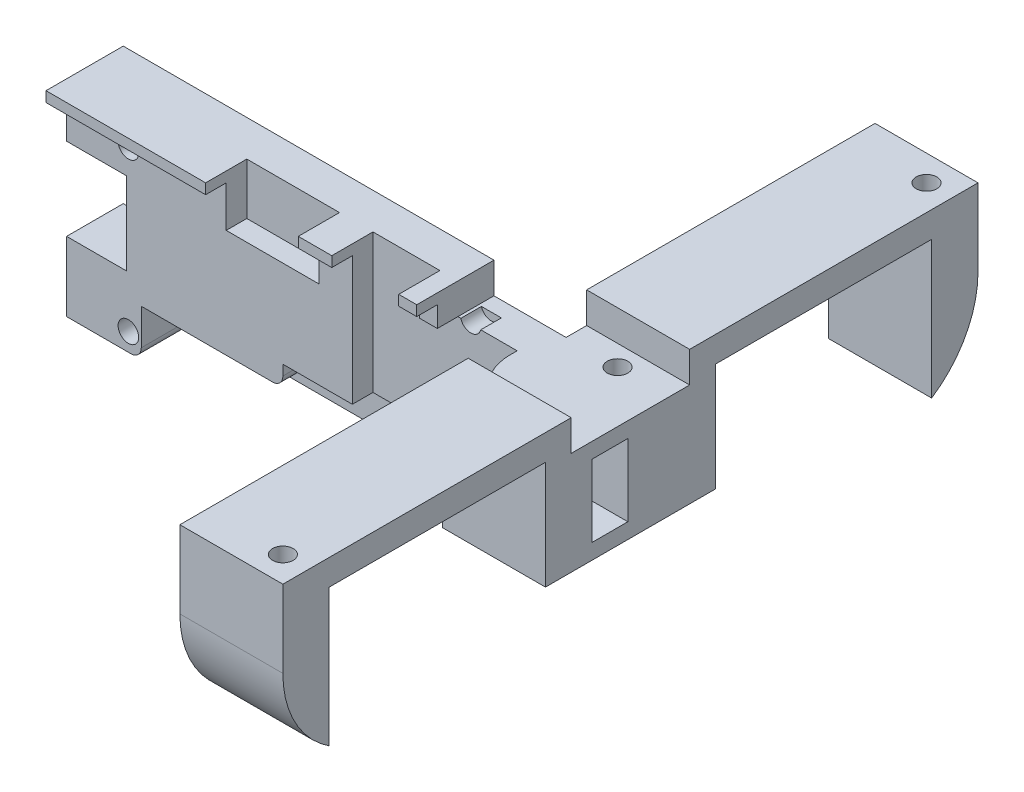
SolidWorks part; units mm, degrees
material "ABS"
ref_plane "Front Plane" through (0, 0, 0) normal (0, 0, 1) x (1, 0, 0)
ref_plane "Top Plane" through (0, 0, 0) normal (0, 1, 0) x (1, 0, 0)
ref_plane "Right Plane" through (0, 0, 0) normal (1, 0, 0) x (0, 0, -1)
sketch "Sketch1" plane through (0, 0, 0) normal (0, 1, 0) x (1, 0, 0)
  line L1 (-40.3176, 43.2333) -> (45.6824, 43.2333)
  line L2 (45.6824, 43.2333) -> (45.6824, -16.7667)
  line L3 (45.6824, -16.7667) -> (65.6824, -16.7667)
  line L4 (65.6824, -16.7667) -> (65.6824, 118.2333)
  line L7 (-40.3176, 43.2333) -> (-40.3176, 58.2333)
  line L8 (-40.3176, 58.2333) -> (45.6824, 58.2333)
  line L9 (45.6824, 58.2333) -> (45.6824, 118.2333)
  line L10 (45.6824, 118.2333) -> (65.6824, 118.2333)
  dimension "D1" = 20
  dimension "D2" = 60
  dimension "D3" = 86
  dimension "D4" = 15
  dimension "D5" = 60
  dimension "D6" = 20
extrude "Boss-Extrude1" add sketch "Sketch1" along normal blind 35
sketch "Sketch2" plane through (65.6824, 0, 0) normal (1, 0, 0) x (0, 0, -1)
  line L1 (-7.7667, 30) -> (34.2333, 30)
  line L2 (-7.7667, 30) -> (-7.7667, 9)
  line L3 (-7.7667, 9) -> (34.2333, 9)
  line L4 (34.2333, 30) -> (34.2333, 9)
  line L5 (-16.7667, 35) -> (-16.7667, 0) construction
  line L6 (50.7333, 24.6294) -> (50.7333, 59.3446) construction
  line L7 (-16.7667, 0) -> (118.2333, 0) construction
  line L9 (109.2333, 9) -> (67.2333, 9)
  line L10 (109.2333, 30) -> (109.2333, 9)
  line L11 (109.2333, 30) -> (67.2333, 30)
  line L12 (67.2333, 30) -> (67.2333, 9)
  dimension "D1" = 21
  dimension "D2" = 42
  dimension "D3" = 9
  dimension "D4" = 9
  dimension "D5" = 7.5
extrude "Cut-Extrude1" cut sketch "Sketch2" against normal up to next
sketch "Sketch3" plane through (45.6824, 0, 0) normal (-1, 0, 0) x (0, 0, 1)
  line L0 (7.7667, 9) -> (7.7667, 30) construction
  line L1 (-34.2333, 9) -> (7.7667, 9) construction
  line L2 (-50.7333, 32.1987) -> (-50.7333, 60.1119) construction
  line L3 (-43.2333, 35) -> (-43.2333, 0) construction
  circle A0 centre (11.2667, 24.75) radius 2
  circle A1 centre (11.2667, 15.25) radius 2
  circle A2 centre (-37.7333, 24.75) radius 2
  circle A3 centre (-37.7333, 15.25) radius 2
  circle A4 centre (-112.7333, 24.75) radius 2
  circle A5 centre (-112.7333, 15.25) radius 2
  circle A6 centre (-63.7333, 15.25) radius 2
  circle A7 centre (-63.7333, 24.75) radius 2
  dimension "D1" = 4
  dimension "D2" = 49
  dimension "D3" = 9.5
  dimension "D4" = 3.5
  dimension "D5" = 6.25
  dimension "D6" = 7.5
extrude "Cut-Extrude2" cut sketch "Sketch3" against normal blind 10
fillet "Fillet1" radius 20 2 edges at (55.6824, 0, 16.7667) (55.6824, 0, -118.2333)
sketch "Sketch6" plane through (65.6824, 0, 0) normal (1, 0, 0) x (0, 0, -1)
  line L0 (34.2333, 9) -> (34.2333, 30) construction
  line L1 (-7.7667, 9) -> (34.2333, 9)
  line L2 (-7.7667, 9) -> (-7.7667, 0)
  line L3 (-7.7667, 0) -> (34.2333, 0)
  line L4 (34.2333, 9) -> (34.2333, 0)
  line L5 (3.2333, 0) -> (98.2333, 0) construction
  line L6 (50.7333, 24.0053) -> (50.7333, 51.0852) construction
  line L7 (67.2333, 9) -> (67.2333, 0)
  line L8 (109.2333, 9) -> (67.2333, 9)
  line L9 (109.2333, 0) -> (67.2333, 0)
  line L10 (109.2333, 9) -> (109.2333, 0)
  dimension "D1" = 7.5
extrude "Cut-Extrude5" cut sketch "Sketch6" against normal up to next
sketch "Sketch7" plane through (-40.3176, 0, 0) normal (-1, 0, 0) x (0, 0, 1)
  line L0 (-58.2333, 0) -> (-43.2333, 0) construction
  line L2 (-58.2333, 35) -> (-43.2333, 35) construction
  line L3 (-43.2333, 35) -> (-43.2333, 0) construction
  circle A0 centre (-50.7333, 28.5) radius 2
  circle A1 centre (-50.7333, 5) radius 2
  dimension "D1" = 4
  dimension "D2" = 5
  dimension "D4" = 6.5
  dimension "D5" = 7.5
extrude "Cut-Extrude6" cut sketch "Sketch7" against normal blind 12
sketch "Sketch8" plane through (0, 0, 0) normal (0, -1, 0) x (1, 0, 0)
  line L1 (45.6824, -67.2333) -> (45.6824, -58.2333) construction
  line L2 (45.6824, -67.2333) -> (65.6824, -67.2333) construction
  line L3 (65.6824, -34.2333) -> (65.6824, -67.2333) construction
  line L4 (45.6824, -34.2333) -> (65.6824, -34.2333) construction
  line L5 (45.6824, -43.2333) -> (45.6824, -34.2333) construction
  line L9 (45.6824, -67.2333) -> (45.6824, -58.2333)
  line L10 (45.6824, -67.2333) -> (65.6824, -67.2333)
  line L11 (65.6824, -34.2333) -> (65.6824, -67.2333)
  line L12 (45.6824, -34.2333) -> (65.6824, -34.2333)
  line L13 (45.6824, -43.2333) -> (45.6824, -34.2333)
  line L16 (45.6824, -43.2333) -> (25.6824, -43.2333)
  line L17 (-40.3176, -43.2333) -> (45.6824, -43.2333) construction
  line L18 (25.6824, -43.2333) -> (25.6824, -58.2333)
  line L19 (45.6824, -58.2333) -> (-40.3176, -58.2333) construction
  line L20 (25.6824, -58.2333) -> (45.6824, -58.2333)
  dimension "D1" = 20
extrude "Cut-Extrude7" cut sketch "Sketch8" against normal blind 9
sketch "Sketch9" plane through (0, 9, 0) normal (0, -1, 0) x (1, 0, 0)
  line L1 (65.6824, -34.2333) -> (45.6824, -34.2333) construction
  line L2 (65.6824, -67.2333) -> (65.6824, -34.2333) construction
  line L3 (45.6824, -67.2333) -> (65.6824, -67.2333) construction
  circle A0 centre (55.6824, -42.2333) radius 2
  circle A1 centre (55.6824, -59.2333) radius 2
  dimension "D4" = 10
  dimension "D5" = 8
  dimension "D6" = 8
extrude "Cut-Extrude8" cut sketch "Sketch9" against normal blind 10
sketch "Sketch10" plane through (0, 35, 0) normal (0, 1, 0) x (1, 0, 0)
  line L0 (45.6824, 62.2333) -> (65.6824, 62.2333)
  line L1 (45.6824, 118.2333) -> (45.6824, 58.2333) construction
  line L2 (65.6824, -16.7667) -> (65.6824, 118.2333) construction
  line L3 (65.6824, 62.2333) -> (65.6824, 39.2333)
  line L4 (65.6824, 39.2333) -> (45.6824, 39.2333)
  line L5 (45.6824, 43.2333) -> (45.6824, -16.7667) construction
  line L7 (45.6824, 39.2333) -> (45.6824, 43.2333)
  line L8 (45.6824, 43.2333) -> (31.6824, 43.2333)
  line L9 (-40.3176, 43.2333) -> (45.6824, 43.2333) construction
  line L10 (31.6824, 43.2333) -> (31.6824, 58.2333)
  line L11 (45.6824, 58.2333) -> (-40.3176, 58.2333) construction
  line L12 (31.6824, 58.2333) -> (45.6824, 58.2333)
  line L13 (45.6824, 58.2333) -> (45.6824, 62.2333)
  dimension "D1" = 5
  dimension "D2" = 5
  dimension "D3" = 14
extrude "Cut-Extrude9" cut sketch "Sketch10" against normal blind 6
sketch "Sketch11" plane through (0, 29, 0) normal (0, 1, 0) x (1, 0, 0)
  line L0 (45.6824, 62.2333) -> (45.6824, 58.2333) construction
  circle A0 centre (55.6824, 58.2333) radius 2
  circle A1 centre (55.6824, 43.2333) radius 2
  dimension "D1" = 4
  dimension "D2" = 10
  dimension "D5" = 0
extrude "Cut-Extrude10" cut sketch "Sketch11" against normal blind 9
sketch "Sketch12" plane through (0, 35, 0) normal (0, 1, 0) x (1, 0, 0)
  line L0 (65.6824, 118.2333) -> (45.6824, 118.2333) construction
  line L1 (45.6824, -16.7667) -> (65.6824, -16.7667) construction
  line L2 (65.6824, -16.7667) -> (65.6824, 39.2333) construction
  line L3 (65.6824, 62.2333) -> (65.6824, 118.2333) construction
  circle A0 centre (60.6824, -11.7667) radius 2
  circle A1 centre (60.6824, 113.2333) radius 2
  dimension "D2" = 4
  dimension "D1" = 5
  dimension "D3" = 5
  dimension "D4" = 5
  dimension "D5" = 5
extrude "Cut-Extrude11" cut sketch "Sketch12" against normal blind 10
sketch "Sketch14" plane through (0, 0, -43.2333) normal (0, 0, 1) x (1, 0, 0)
  line L0 (-40.3176, 35) -> (-40.3176, 0) construction
  line L1 (-40.3176, 33) -> (42.6824, 33)
  line L2 (-40.3176, 33) -> (-40.3176, 0)
  line L3 (-40.3176, 0) -> (42.6824, 0)
  line L4 (42.6824, 33) -> (42.6824, 0)
  line L5 (-40.3176, 0) -> (25.6824, 0) construction
  line L7 (-40.3176, 35) -> (31.6824, 35) construction
  dimension "D1" = 83
  dimension "D2" = 2
extrude "Cut-Extrude13" cut sketch "Sketch14" against normal blind 4
sketch "Sketch15" plane through (0, 0, -47.2333) normal (0, 0, 1) x (1, 0, 0)
  line L1 (1.6824, 8) -> (33.6824, 8)
  line L3 (-25.8176, 0) -> (33.6824, 0)
  line L4 (33.6824, 8) -> (33.6824, 0)
  line L5 (31.6824, 29) -> (31.6824, 33) construction
  line L6 (-40.3176, 0) -> (25.6824, 0) construction
  line L7 (31.6824, 33) -> (-40.3176, 33) construction
  line L11 (1.6824, 8) -> (1.6824, 4)
  line L12 (1.6824, 4) -> (-25.8176, 4)
  line L13 (-25.8176, 4) -> (-25.8176, 0)
  line L14 (-40.3176, 33) -> (-40.3176, 0) construction
  dimension "D1" = 25
  dimension "D2" = 32
  dimension "D3" = 2
  dimension "D4" = 29
  dimension "D5" = 14.5
extrude "Cut-Extrude14" cut sketch "Sketch15" against normal blind 6.5
sketch "Sketch16" plane through (0, 0, 0) normal (0, -1, 0) x (1, 0, 0)
  line L0 (25.6824, -58.2333) -> (-40.3176, -58.2333) construction
  line L1 (-40.3176, -47.2333) -> (-25.8176, -47.2333)
  line L2 (-40.3176, -47.2333) -> (-40.3176, -58.2333)
  line L3 (-40.3176, -58.2333) -> (-25.8176, -58.2333)
  line L4 (-25.8176, -47.2333) -> (-25.8176, -58.2333)
  line L5 (-25.8176, -53.7333) -> (-25.8176, -47.2333) construction
extrude "Boss-Extrude2" add sketch "Sketch16" along normal blind 5
sketch "Sketch13" plane through (0, 0, -43.2333) normal (0, 0, 1) x (1, 0, 0)
  line L1 (-38.3176, 32) -> (36.6824, 32) construction
  line L2 (-38.3176, 32) -> (-38.3176, -4) construction
  line L3 (-38.3176, -4) -> (36.6824, -4) construction
  line L4 (36.6824, 32) -> (36.6824, -4) construction
  line L5 (-40.3176, 33) -> (-40.3176, -5) construction
  line L6 (-40.3176, 35) -> (31.6824, 35) construction
  circle A0 centre (-28.3176, 29.5) radius 2
  circle A1 centre (34.1824, 29.5) radius 2
  circle A2 centre (34.1824, -1.5) radius 2
  circle A3 centre (-28.3176, -1.5) radius 2
  dimension "D3" = 4
  dimension "D1" = 31
  dimension "D2" = 62.5
  dimension "D4" = 75
  dimension "D5" = 36
  dimension "D6" = 2.5
  dimension "D7" = 10
  dimension "D8" = 2
  dimension "D9" = 5.5
extrude "Cut-Extrude12" cut sketch "Sketch13" against normal blind 12
fillet "Fillet2" radius 2 1 edges at (-25.8176, -5, -52.7333)
fillet "Fillet3" radius 2 1 edges at (1.6824, 4, -50.4833)
sketch "Sketch17" plane through (0, 0, -43.2333) normal (0, 0, 1) x (1, 0, 0)
  line L1 (43.1824, -5) -> (15.1824, -5)
  line L2 (43.1824, -5) -> (43.1824, 29)
  line L4 (15.1824, -5) -> (15.1824, 35)
  line L5 (-40.3176, 35) -> (31.6824, 35) construction
  line L7 (-9.3176, 35) -> (8.6824, 35)
  line L8 (-9.3176, 35) -> (-9.3176, 25)
  line L9 (-9.3176, 25) -> (8.6824, 25)
  line L10 (8.6824, 35) -> (8.6824, 25)
  line L11 (15.1824, 35) -> (28.1824, 35)
  line L12 (28.1824, 35) -> (28.1824, 29)
  line L13 (28.1824, 29) -> (43.1824, 29)
  circle A1 centre (-28.3176, 29.5) radius 2 construction
  dimension "D3" = 19
  dimension "D1" = 13
  dimension "D2" = 6.5
  dimension "D4" = 18
  dimension "D5" = 10
  dimension "D6" = 40
  dimension "D7" = 15
  dimension "D8" = 6
extrude "Cut-Extrude15" cut sketch "Sketch17" against normal blind 8
sketch "Sketch20" plane through (0, 0, -47.2333) normal (0, 0, 1) x (1, 0, 0)
  line L0 (-40.3176, 33) -> (-40.3176, -5) construction
  line L1 (-40.3176, 24.5) -> (-32.3176, 24.5)
  line L2 (-40.3176, 24.5) -> (-40.3176, 8.5)
  line L3 (-40.3176, 8.5) -> (-32.3176, 8.5)
  line L4 (-32.3176, 24.5) -> (-32.3176, 8.5)
  circle A0 centre (-28.3176, 29.5) radius 2 construction
  dimension "D1" = 8
  dimension "D2" = 16
  dimension "D3" = 5
extrude "Cut-Extrude18" cut sketch "Sketch20" against normal up to next
chamfer "Chamfer1" distance 10 angle 20 1 edges at (-32.3176, 16.5, -47.2333) first distance on face at (-32.3176, 16.5, -52.7333)
sketch "Sketch21" plane through (0, 0, -47.2333) normal (0, 0, 1) x (1, 0, 0)
  line L0 (-38.3176, 32) -> (36.6824, 32) construction
  line L1 (-38.3176, 32) -> (-38.3176, -4) construction
  line L2 (-38.3176, -4) -> (36.6824, -4) construction
  line L3 (36.6824, 32) -> (36.6824, -4) construction
  line L5 (33.1824, 26.5) -> (39.1824, 26.5) construction
  line L6 (33.1824, 26.5) -> (33.1824, 14) construction
  line L7 (33.1824, 14) -> (39.1824, 14)
  line L8 (39.1824, 26.5) -> (39.1824, 14) construction
  line L9 (32.6824, 13) -> (37.6824, 13) construction
  line L10 (32.6824, 13) -> (32.6824, 3) construction
  line L11 (32.6824, 3) -> (37.6824, 3) construction
  line L12 (37.6824, 13) -> (37.6824, 3) construction
  circle A0 centre (-28.3176, 29.5) radius 2
  circle A1 centre (34.1824, 29.5) radius 2
  circle A2 centre (34.1824, -1.5) radius 2
  circle A3 centre (-28.3176, -1.5) radius 2
  dimension "D3" = 4
  dimension "D1" = 31
  dimension "D2" = 62.5
  dimension "D4" = 75
  dimension "D5" = 36
  dimension "D6" = 2.5
  dimension "D7" = 10
  dimension "D8" = 12.5
  dimension "D9" = 6
  dimension "D10" = 3.5
  dimension "D11" = 5.5
  dimension "D12" = 5
  dimension "D13" = 10
  dimension "D14" = 7
  dimension "D15" = 1
sketch "Sketch22" plane through (65.6824, 0, 0) normal (1, 0, 0) x (0, 0, -1)
  line L0 (39.2333, 29) -> (62.2333, 29) construction
  line L1 (43.2333, 26) -> (50.2333, 26)
  line L2 (43.2333, 26) -> (43.2333, 12)
  line L3 (43.2333, 12) -> (50.2333, 12)
  line L4 (50.2333, 26) -> (50.2333, 12)
  line L5 (39.2333, 29) -> (39.2333, 35) construction
  dimension "D1" = 14
  dimension "D2" = 3
  dimension "D3" = 4
  dimension "D4" = 7
extrude "Cut-Extrude19" cut sketch "Sketch22" against normal up to next
fillet "Fillet8" radius 10 2 edges at (43.1824, 10.5, -43.2333) (43.1824, 27.5, -43.2333)
